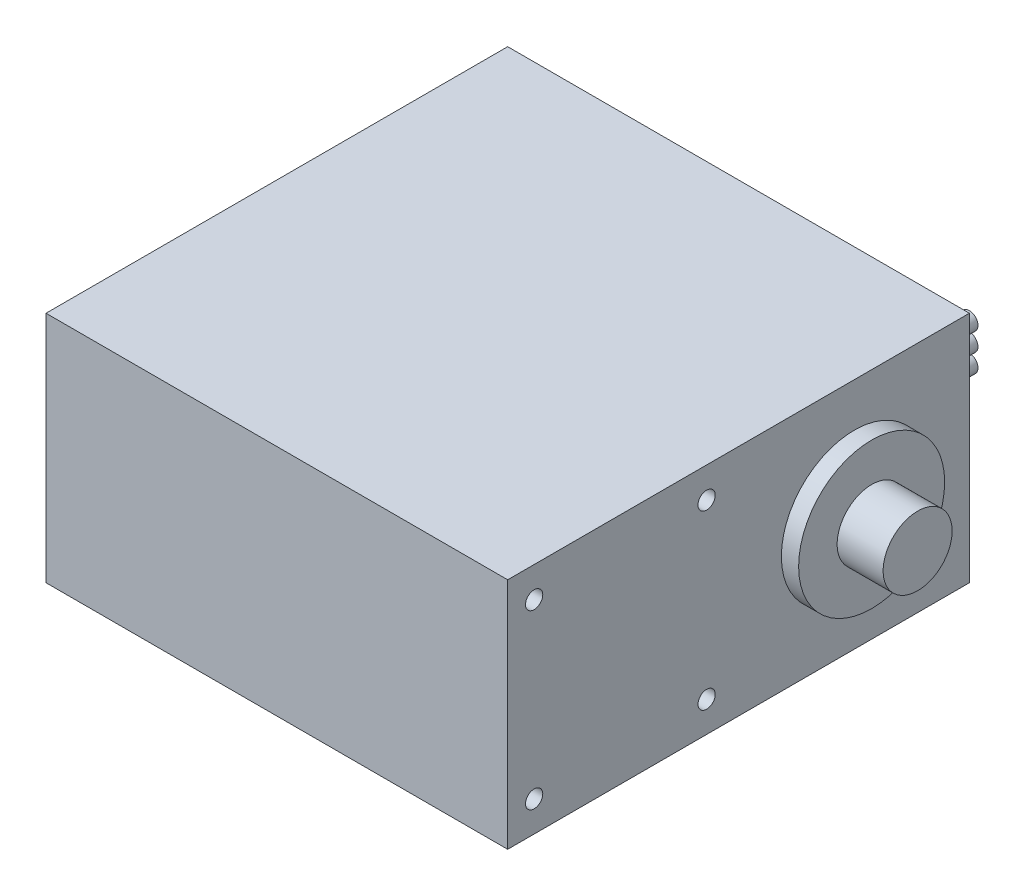
SolidWorks part; units mm, degrees
ref_plane "Plan de face" through (0, 0, 0) normal (0, 0, 1) x (1, 0, 0)
ref_plane "Plan de dessus" through (0, 0, 0) normal (0, 1, 0) x (1, 0, 0)
ref_plane "Plan de droite" through (0, 0, 0) normal (1, 0, 0) x (0, 0, -1)
sketch "Esquisse1" plane through (0, 0, 0) normal (0, 1, 0) x (1, 0, 0)
  line L0 (-20.075, -20.075) -> (20.075, 20.075) construction
  line L1 (-20.075, -20.075) -> (20.075, -20.075)
  line L2 (-20.075, -20.075) -> (-20.075, 20.075)
  line L3 (-20.075, 20.075) -> (20.075, 20.075)
  line L4 (20.075, -20.075) -> (20.075, 20.075)
  point P4 (0, 0)
  dimension "D1" = 40.15
  dimension "D2" = 40.15
extrude "Boss.-Extru.1" add sketch "Esquisse1" along normal mid plane 20.3
ref_plane "Plan1" through (0, 0, -10.075) normal (0, 0, -1) x (-1, 0, 0)
ref_axis "Axe1" through (-34.7724, 0, -10.075) along (1, 0, 0)
sketch "Esquisse3" plane through (-20.075, 0, 0) normal (-1, 0, 0) x (0, 0, 1)
  circle A0 centre (-10.075, 0) radius 6.15
  dimension "D1" = 12.3
extrude "Boss.-Extru.2" add sketch "Esquisse3" along normal blind 1.5
sketch "Esquisse4" plane through (-21.575, 0, 0) normal (-1, 0, 0) x (0, 0, 1)
  circle A0 centre (-10.075, 0) radius 2.9
  dimension "D1" = 5.8
extrude "Boss.-Extru.3" add sketch "Esquisse4" along normal blind 4.35
hole_wizard "Diamètre du perçage Ø3.0 (3)1" positions "Esquisse11" profile "Esquisse12" hole size "Ø3.0" standard "DIN"
sketch "Esquisse11" plane through (-25.925, 0, 0) normal (-1, 0, 0) x (0, 0, 1)
  point P0 (-10.075, 0)
sketch "Esquisse12" plane through (-25.925, 0, -10.075) normal (0, 1, 0) x (0, 0, 1)
  line L0 (0, 0) -> (0, 6.9013)
  line L1 (0, 6.9013) -> (1.5, 6)
  line L2 (1.5, 6) -> (1.5, 0)
  line L5 (1.5, 0) -> (0, 0)
  line L10 (0, 6.9013) -> (-1.5, 6) construction
  line L11 (0, -6.35) -> (0, 107.95) construction
  dimension "Diamètre du perçage" = 3
  dimension "Profondeur du perçage" = 6
  dimension "Angle de pointe" = 118
sketch "Esquisse5" plane through (20.075, 0, 0) normal (1, 0, 0) x (0, 0, -1)
  circle A0 centre (10.075, 0) radius 6.35
  dimension "D1" = 12.7
extrude "Boss.-Extru.4" add sketch "Esquisse5" along normal blind 1.5
sketch "Esquisse6" plane through (21.575, 0, 0) normal (1, 0, 0) x (0, 0, -1)
  circle A0 centre (10.075, 0) radius 3
  dimension "D1" = 6
extrude "Boss.-Extru.5" add sketch "Esquisse6" along normal blind 4
sketch "Esquisse7" plane through (0, 0, -20.075) normal (0, 0, -1) x (-1, 0, 0)
  line L0 (-20.075, -10.15) -> (20.075, -10.15) construction
  line L2 (-14.075, 4.15) -> (-14.075, -4.15)
  line L3 (-14.075, -4.15) -> (-10.075, -4.15)
  line L4 (-10.075, 4.15) -> (-10.075, -4.15)
  line L5 (34.7724, 0) -> (-26.6964, 0) construction
  line L6 (0, 0) -> (-20.075, 0) construction
  line L7 (-20.075, 6.35) -> (-20.075, -6.35) construction
  line L8 (-14.075, 4.15) -> (-10.075, 4.15)
  line L9 (-20.075, 10.15) -> (-20.075, -10.15) construction
  point P9 (-14.075, 0)
  point P15 (-10.075, 0)
  dimension "D1" = 6
  dimension "D2" = 6
  dimension "D3" = 4
extrude "Boss.-Extru.6" add sketch "Esquisse7" along normal blind 4
sketch "Esquisse8" plane through (0, 0, -24.075) normal (0, 0, -1) x (-1, 0, 0)
  line L0 (-10.075, 0) -> (-14.075, 0) construction
  line L1 (-10.075, -4.15) -> (-10.075, 4.15) construction
  line L2 (-14.075, 4.15) -> (-14.075, -4.15) construction
  line L3 (-12.075, 0) -> (-12.075, -4.15) construction
  line L4 (-14.075, -4.15) -> (-10.075, -4.15) construction
  circle A0 centre (-12.075, 0) radius 0.75
  circle A1 centre (-12.075, -1.6) radius 0.75
  circle A2 centre (-12.075, 1.6) radius 0.75
  dimension "D1" = 1.5
  dimension "D2" = 1.6
extrude "Boss.-Extru.8" add sketch "Esquisse8" along normal blind 4
sketch "Esquisse9" plane through (20.075, 0, 0) normal (1, 0, 0) x (0, 0, -1)
  line L0 (0, 0) -> (-20.075, 0) construction
  line L1 (-20.075, 10.15) -> (-20.075, -10.15) construction
  line L2 (-17.775, -7.5) -> (-17.775, 7.5) construction
  line L3 (-17.775, 7.5) -> (-2.775, 7.5) construction
  line L4 (-2.775, 7.5) -> (-2.775, -7.5) construction
  line L5 (-17.775, -7.5) -> (-2.775, -7.5) construction
  circle A0 centre (-17.775, 7.5) radius 0.75
  circle A1 centre (-2.775, 7.5) radius 0.75
  circle A2 centre (-17.775, -7.5) radius 0.75
  circle A3 centre (-2.775, -7.5) radius 0.75
  point P10 (-2.775, 0)
  point P11 (-17.775, 0)
  dimension "D3" = 1.5
  dimension "D1" = 15
  dimension "D2" = 2.3
extrude "Enlèv. mat.-Extru.1" cut sketch "Esquisse9" against normal blind 5
sketch "Esquisse10" plane through (-20.075, 0, 0) normal (-1, 0, 0) x (0, 0, 1)
  line L0 (0, 0) -> (20.075, 0) construction
  line L1 (20.075, 10.15) -> (20.075, -10.15) construction
  line L2 (10.275, 0) -> (10.275, 7) construction
  circle A0 centre (10.275, 0) radius 7 construction
  circle A1 centre (17.275, 0) radius 0.75
  circle A2 centre (10.275, 7) radius 0.75
  circle A3 centre (10.275, -7) radius 0.75
  point P7 (17.275, 0)
  dimension "D1" = 14
  dimension "D2" = 2.8
  dimension "D3" = 1.5
extrude "Enlèv. mat.-Extru.2" cut sketch "Esquisse10" against normal blind 5
